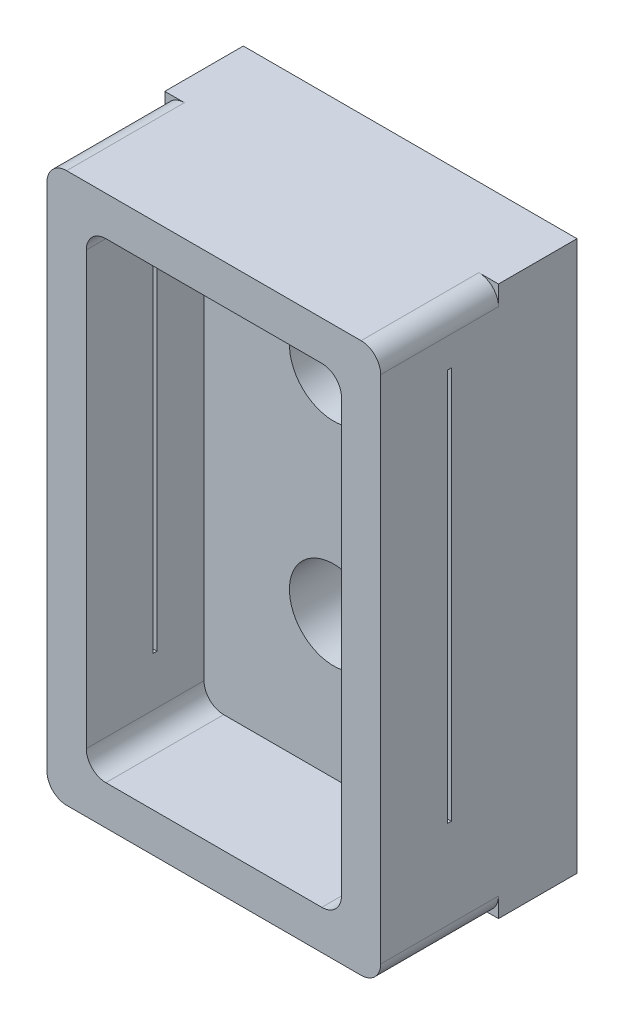
SolidWorks part; units mm, degrees
ref_plane "Front Plane" through (0, 0, 0) normal (0, 0, 1) x (1, 0, 0)
ref_plane "Top Plane" through (0, 0, 0) normal (0, 1, 0) x (1, 0, 0)
ref_plane "Right Plane" through (0, 0, 0) normal (1, 0, 0) x (0, 0, -1)
sketch "Sketch1" plane through (0, 0, 0) normal (0, 0, 1) x (1, 0, 0)
  line L1 (12.065, -20.2914) -> (-9.525, -20.2914)
  line L2 (12.065, -20.2914) -> (12.065, 15.2686)
  line L3 (12.065, 15.2686) -> (-9.525, 15.2686)
  line L4 (-9.525, -20.2914) -> (-9.525, 15.2686)
  circle A0 centre (1.397, 5.1086) radius 2.8575
  circle A1 centre (1.397, -8.6074) radius 2.8575
  point P0 (0, 0)
  dimension "D3" = 5.715
  dimension "D4" = 5.715
  dimension "D6" = 10.668
  dimension "D7" = 10.16
  dimension "D1" = 21.59
  dimension "D2" = 35.56
  dimension "D5" = 13.716
extrude "Boss-Extrude1" add sketch "Sketch1" along normal blind 12.7
sketch "Sketch2" plane through (0, 0, 12.7) normal (0, 0, 1) x (1, 0, 0)
  line L1 (9.525, -17.7514) -> (-6.985, -17.7514)
  line L2 (9.525, -17.7514) -> (9.525, 12.7286)
  line L3 (9.525, 12.7286) -> (-6.985, 12.7286)
  line L4 (-6.985, -17.7514) -> (-6.985, 12.7286)
  line L5 (12.065, -20.2914) -> (12.065, 15.2686) construction
  line L8 (12.065, 15.2686) -> (-9.525, 15.2686) construction
  point P0 (0, 0)
  dimension "D1" = 16.51
  dimension "D2" = 2.54
  dimension "D3" = 30.48
  dimension "D4" = 2.54
extrude "Cut-Extrude1" cut sketch "Sketch2" against normal blind 7.62
fillet "Fillet1" radius 1.27 8 edges at (-6.985, 12.7286, 8.89) (-6.985, -17.7514, 8.89) (9.525, -17.7514, 8.89) (9.525, 12.7286, 8.89) (-9.525, -20.2914, 6.35) (-9.525, 15.2686, 6.35) (12.065, 15.2686, 6.35) (12.065, -20.2914, 6.35)
sketch "Sketch3" plane through (12.065, 0, 0) normal (1, 0, 0) x (0, 0, -1)
  line L0 (-8.382, -13.3064) -> (-8.128, -13.3064)
  line L4 (-8.128, -13.3064) -> (-8.128, 12.0936)
  line L5 (-8.128, 12.0936) -> (-8.382, 12.0936)
  line L6 (-8.382, -13.3064) -> (-8.382, 12.0936)
  line L7 (0, -19.0214) -> (0, 13.9986) construction
  point P5 (-7.62, 0)
  dimension "D1" = 0.254
  dimension "D2" = 25.4
  dimension "D3" = 8.128
extrude "Cut-Extrude3" cut sketch "Sketch3" against normal through all both and the other way through all from surface starting at face at (12.065, -2.5114, 6.35)
extrude "Boss-Extrude2" add sketch "Sketch1<2>" along normal blind 5.08
sketch "Sketch1<2>" plane through (0, 0, 0) normal (0, 0, 1) x (1, 0, 0) same geometry as "Sketch1"
